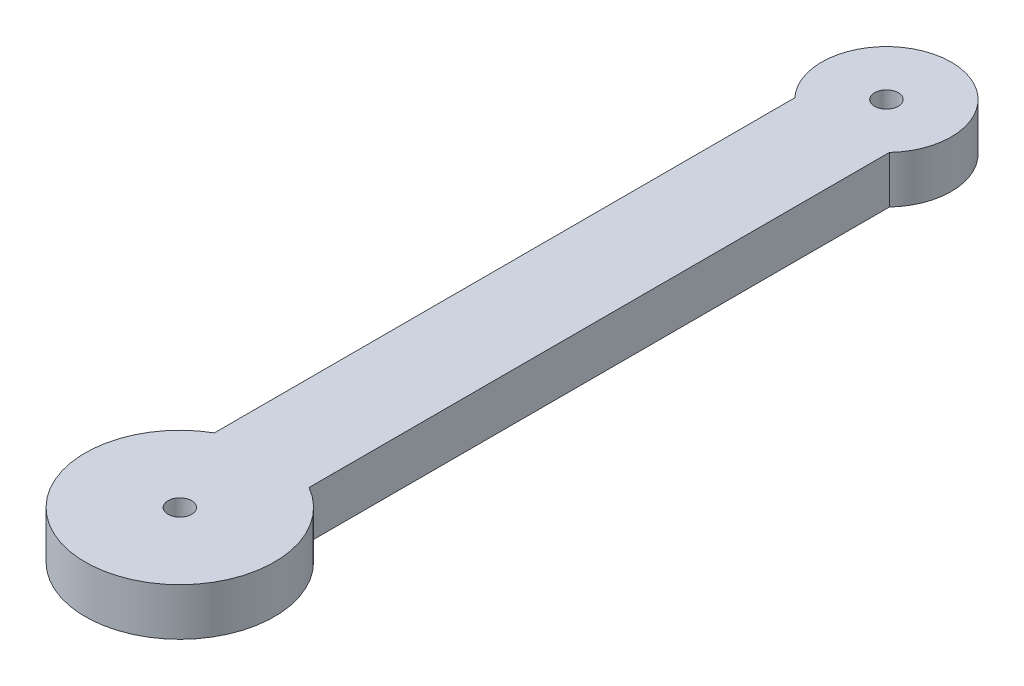
SolidWorks part; units mm, degrees
ref_plane "Front Plane" through (0, 0, 0) normal (0, 0, 1) x (1, 0, 0)
ref_plane "Top Plane" through (0, 0, 0) normal (0, 1, 0) x (1, 0, 0)
ref_plane "Right Plane" through (0, 0, 0) normal (1, 0, 0) x (0, 0, -1)
sketch "Sketch2" plane through (0, 0, 0) normal (0, 1, 0) x (1, 0, 0)
  line L0 (-2.5, 35) -> (-2.5, 4.3301)
  line L1 (2.5, 35) -> (2.5, 4.3301)
  circle A0 centre (0, 0) radius 0.625
  arc A1 (-2.5, 4.3301) -> (2.5, 4.3301) centre (0, 0) ccw
  circle A2 centre (0, 37.3428) radius 0.625
  arc A3 (2.5, 35) -> (-2.5, 35) centre (0, 37.3428) ccw
  point P2 (0, 0)
  point P5 (0, 0)
  point P10 (0, 0)
  dimension "D1" = 1.25
  dimension "D2" = 5
  dimension "D3" = 3.4261
  dimension "D4" = 2.5
  dimension "D5" = 35
extrude "Boss-Extrude1" add sketch "Sketch2" along normal blind 2.5
